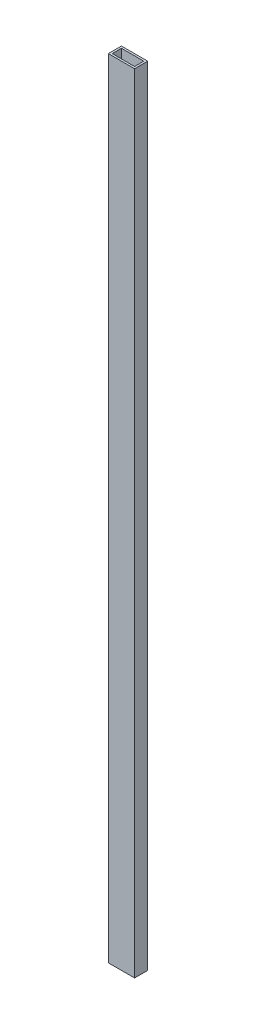
SolidWorks part; units mm, degrees
ref_plane "Спереди" through (0, 0, 0) normal (0, 0, 1) x (1, 0, 0)
ref_plane "Сверху" through (0, 0, 0) normal (0, 1, 0) x (1, 0, 0)
ref_plane "Справа" through (0, 0, 0) normal (1, 0, 0) x (0, 0, -1)
sketch "Эскиз1" plane through (0, 0, 0) normal (0, 1, 0) x (1, 0, 0)
  line L1 (-20, 10) -> (20, 10)
  line L2 (-20, 10) -> (-20, -10)
  line L3 (-20, -10) -> (20, -10)
  line L4 (20, 10) -> (20, -10)
  line L5 (-20, 10) -> (20, -10) construction
  line L6 (-20, -10) -> (20, 10) construction
  point P0 (0, 0)
  dimension "D1" = 40
  dimension "D2" = 20
extrude "Вытянуть-Тонкостенный1" add sketch "Эскиз1" along normal blind 1200 thin thin type one direction reverse wall 3
